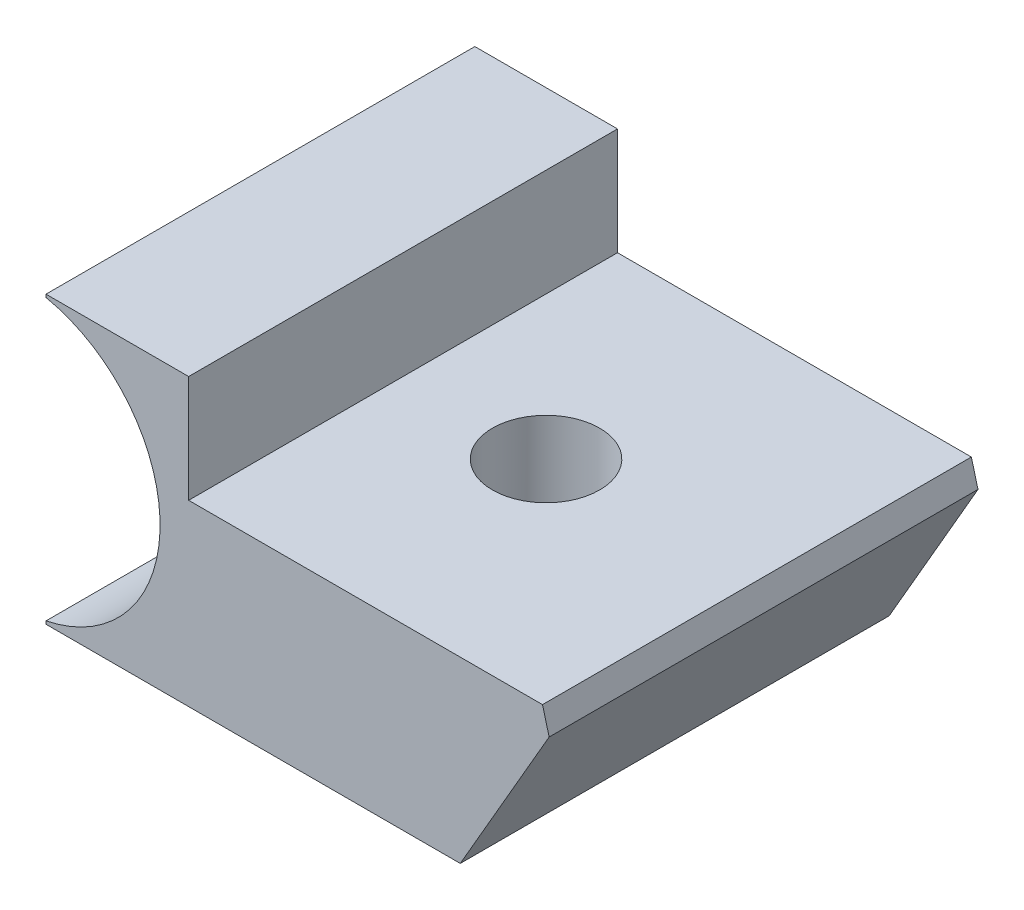
SolidWorks part; units mm, degrees
material "Alloy Steel"
ref_plane "Front Plane" through (0, 0, 0) normal (0, 0, 1) x (1, 0, 0)
ref_plane "Top Plane" through (0, 0, 0) normal (0, 1, 0) x (1, 0, 0)
ref_plane "Right Plane" through (0, 0, 0) normal (1, 0, 0) x (0, 0, -1)
sketch "Sketch1" plane through (0, 0, 0) normal (0, 0, 1) x (1, 0, 0)
  line L1 (2.5655, 0) -> (50.8, 0)
  line L3 (2.5655, 25.4) -> (15.24, 25.4)
  line L4 (50.8, 0) -> (50.8, 15.875)
  line L5 (2.5655, 25.4) -> (2.5655, 25.1382)
  line L6 (15.24, 25.4) -> (15.24, 15.875)
  line L7 (15.24, 15.875) -> (50.8, 15.875)
  line L8 (2.5655, 0.2618) -> (2.5655, 0)
  arc A1 (2.5655, 0.2618) -> (2.5655, 25.1382) centre (0, 12.7) ccw
  dimension "D2" = 25.4
  dimension "D3" = 9.525
extrude "Boss-Extrude1" add sketch "Sketch1" along normal blind 38.1
chamfer "Chamfer1" distance 11.43 angle 60 1 edges at (50.8, 0, 19.05) first distance on face at (26.6828, 0, 19.05)
hole_wizard "3/8 (0.375) Diameter Hole1" positions "Sketch5" profile "Sketch3" hole size "3/8" standard "ANSI Inch" end condition through all
sketch "Sketch5" plane through (0, 25.4, 0) normal (0, 1, 0) x (1, 0, 0)
  line L1 (48.5354, -38.1) -> (48.5354, 0) construction
  point P0 (27.94, -19.05)
  dimension "D1" = 20.5954
sketch "Sketch3" plane through (27.94, 25.4, 19.05) normal (1, 0, 0) x (0, 0, 1)
  line L0 (0, 0) -> (0, 25.4)
  line L1 (0, 25.4) -> (4.7625, 25.4)
  line L2 (4.7625, 25.4) -> (4.7625, 0)
  line L5 (4.7625, 0) -> (0, 0)
  line L11 (0, -6.35) -> (0, 107.95) construction
  dimension "Thru Hole Dia." = 9.525
  dimension "Thru Hole Depth" = 25.4
chamfer "Chamfer2" distance 2.54 angle 45 1 edges at (48.5354, 15.875, 19.05) first distance on face at (43.9527, 7.9375, 19.05)
